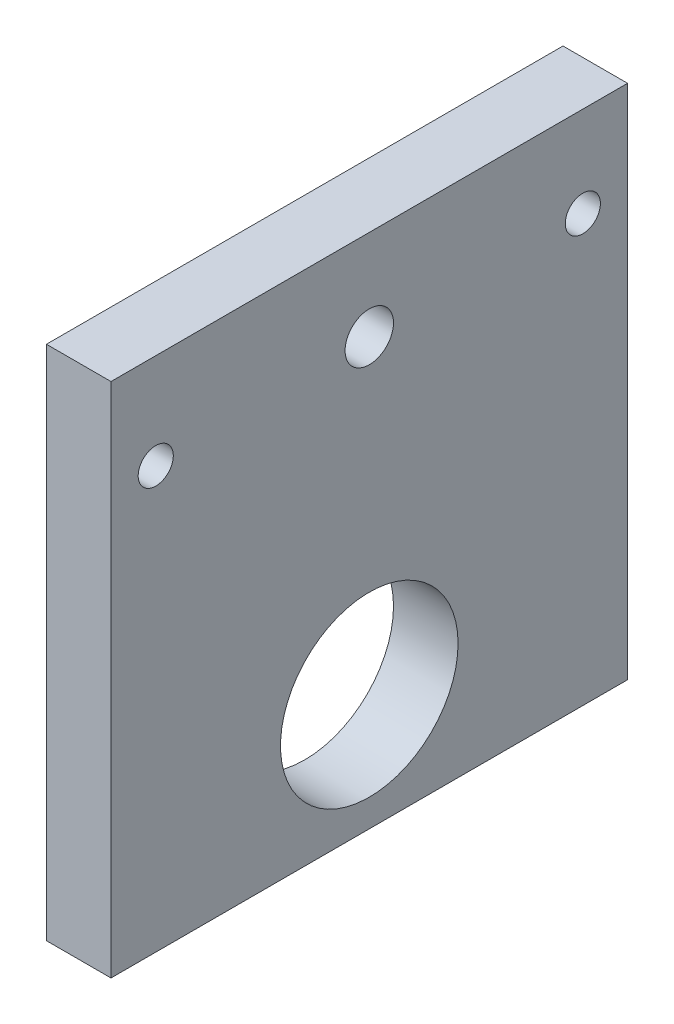
SolidWorks part; units mm, degrees
ref_plane "Front Plane" through (0, 0, 0) normal (0, 0, 1) x (1, 0, 0)
ref_plane "Top Plane" through (0, 0, 0) normal (0, 1, 0) x (1, 0, 0)
ref_plane "Right Plane" through (0, 0, 0) normal (1, 0, 0) x (0, 0, -1)
sketch "Sketch1" plane through (0, 0, 0) normal (1, 0, 0) x (0, 0, -1)
  line L1 (-25.4, -25.4) -> (25.4, -25.4)
  line L2 (-25.4, -25.4) -> (-25.4, 25.4)
  line L3 (-25.4, 25.4) -> (25.4, 25.4)
  line L4 (25.4, -25.4) -> (25.4, 25.4)
  line L5 (-25.4, -25.4) -> (25.4, 25.4) construction
  line L6 (-25.4, 25.4) -> (25.4, -25.4) construction
  point P0 (0, 0)
  dimension "D1" = 50.8
  dimension "D2" = 50.8
extrude "Boss-Extrude1" add sketch "Sketch1" along normal blind 6.35
hole_wizard "11/16 (0.6875) Diameter Hole1" positions "Sketch9" profile "Sketch8" hole size "11/16" standard "ANSI Inch"
sketch "Sketch9" plane through (6.35, 0, 0) normal (1, 0, 0) x (0, 0, -1)
  line L0 (-25.4, -25.4) -> (25.4, -25.4) construction
  point P0 (0, -13.97)
  dimension "D1" = 11.43
sketch "Sketch8" plane through (6.35, -13.97, 0) normal (0, 1, 0) x (0, 0, -1)
  line L0 (0, 0) -> (0, 75.3503)
  line L1 (0, 75.3503) -> (8.7312, 70.104)
  line L2 (8.7312, 70.104) -> (8.7312, 0)
  line L5 (8.7312, 0) -> (0, 0)
  line L10 (0, 75.3503) -> (-8.7313, 70.104) construction
  line L11 (0, -6.35) -> (0, 107.95) construction
  dimension "Hole Dia." = 17.4625
  dimension "Hole Depth" = 70.104
  dimension "Drill Angle" = 118
hole_wizard "3/16 (0.1875) Diameter Hole1" positions "Sketch3" profile "Sketch2" hole size "3/16" standard "ANSI Inch"
sketch "Sketch3" plane through (6.35, 0, 0) normal (1, 0, 0) x (0, 0, -1)
  circle A0 centre (0, -13.97) radius 8.7312 construction
  point P0 (0, 16.51)
  dimension "D1" = 30.48
  dimension "D2" = 0
sketch "Sketch2" plane through (6.35, 16.51, 0) normal (0, 1, 0) x (0, 0, -1)
  line L0 (0, 0) -> (0, 71.5348)
  line L1 (0, 71.5348) -> (2.3812, 70.104)
  line L2 (2.3812, 70.104) -> (2.3812, 0)
  line L5 (2.3812, 0) -> (0, 0)
  line L10 (0, 71.5348) -> (-2.3813, 70.104) construction
  line L11 (0, -6.35) -> (0, 107.95) construction
  dimension "Hole Dia." = 4.7625
  dimension "Hole Depth" = 70.104
  dimension "Drill Angle" = 118
hole_wizard "#29 (0.136) Diameter Hole1" positions "Sketch5" profile "Sketch4" hole size "#29" standard "ANSI Inch"
sketch "Sketch5" plane through (6.35, 0, 0) normal (1, 0, 0) x (0, 0, -1)
  circle A0 centre (0, 16.51) radius 2.3812 construction
  point P0 (21, 16.51)
  point P2 (-21, 16.0214)
  dimension "D1" = 0.4886
  dimension "D2" = 0
  dimension "D3" = 21
  dimension "D4" = 42
sketch "Sketch4" plane through (6.35, 16.51, -21) normal (0, 1, 0) x (0, 0, -1)
  line L0 (0, 0) -> (0, 71.1418)
  line L1 (0, 71.1418) -> (1.7272, 70.104)
  line L2 (1.7272, 70.104) -> (1.7272, 0)
  line L5 (1.7272, 0) -> (0, 0)
  line L10 (0, 71.1418) -> (-1.7272, 70.104) construction
  line L11 (0, -6.35) -> (0, 107.95) construction
  dimension "Hole Dia." = 3.4544
  dimension "Hole Depth" = 70.104
  dimension "Drill Angle" = 118
